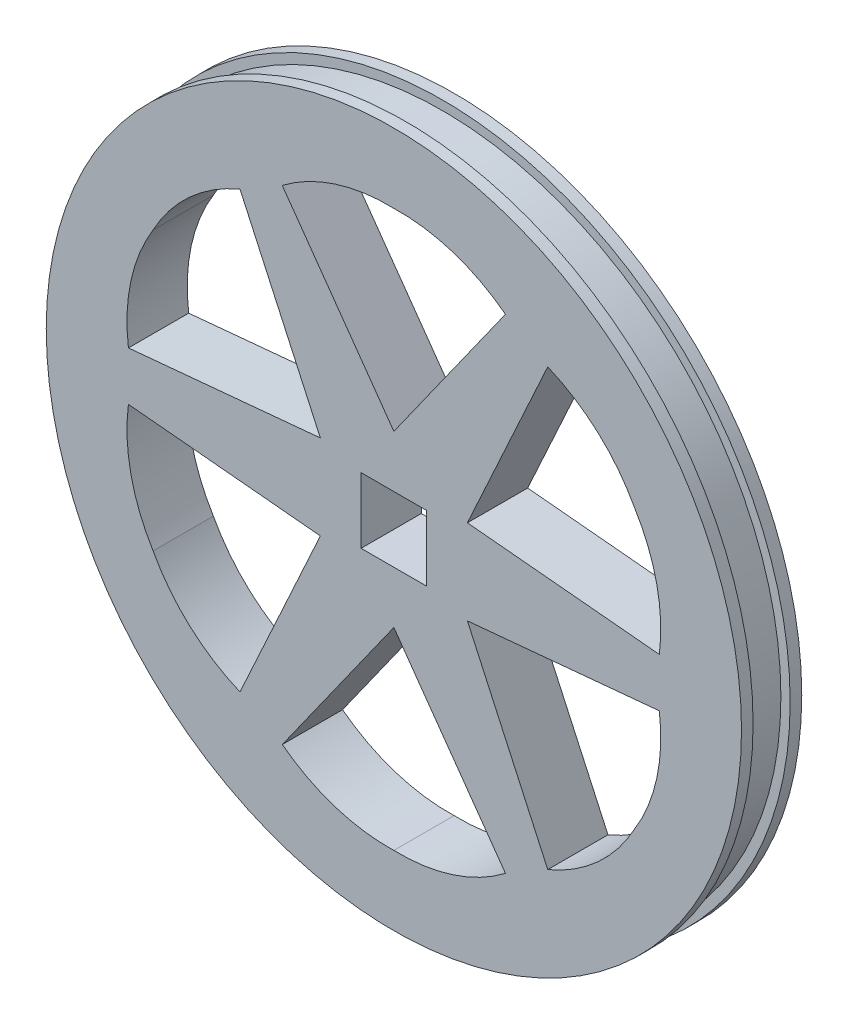
SolidWorks part; units mm, degrees
ref_plane "Front Plane" through (0, 0, 0) normal (0, 0, 1) x (1, 0, 0)
ref_plane "Top Plane" through (0, 0, 0) normal (0, 1, 0) x (1, 0, 0)
ref_plane "Right Plane" through (0, 0, 0) normal (1, 0, 0) x (0, 0, -1)
sketch "Sketch1" plane through (0, 0, 0) normal (0, 0, 1) x (1, 0, 0)
  line L1 (3.5355, -3.5355) -> (-3.5355, -3.5355)
  line L2 (3.5355, -3.5355) -> (3.5355, 3.5355)
  line L3 (3.5355, 3.5355) -> (-3.5355, 3.5355)
  line L4 (-3.5355, -3.5355) -> (-3.5355, 3.5355)
  line L5 (3.5355, -3.5355) -> (-3.5355, 3.5355) construction
  line L6 (3.5355, 3.5355) -> (-3.5355, -3.5355) construction
  circle A0 centre (0, 0) radius 37.5
  circle A1 centre (0, 0) radius 5 construction
  dimension "D1" = 75
  dimension "D2" = 10
extrude "Boss-Extrude1" add sketch "Sketch1" along normal mid plane 6.5
sketch "Sketch2" plane through (0, 0, 0) normal (0, 0, 1) x (1, 0, 0)
  line L0 (0, 0) -> (0, 32.5712) construction
  line L1 (0, 9.1586) -> (-12.0371, 26.1152)
  line L2 (0, 9.1586) -> (12.0371, 26.1152)
  arc A0 (-12.0371, 26.1152) -> (0, 29.9881) centre (-0.5568, 11.0765) cw
  arc A1 (12.0371, 26.1152) -> (0, 29.9881) centre (0.5568, 11.0765) ccw
extrude "Cut-Extrude1" cut sketch "Sketch2" along normal mid plane 8
pattern_circular "CirPattern1" count 6 over 360 about axis through (0, 0, 3.25) along (0, 0, -1) of "Cut-Extrude1" reverse direction yes
sketch "Sketch3" plane through (0, 0, 0) normal (0, 0, 1) x (1, 0, 0)
  circle A0 centre (0, 0) radius 37.5
  circle A1 centre (0, 0) radius 36.5
  circle A2 centre (0, 0) radius 37.5 construction
  dimension "D1" = 1
extrude "Cut-Extrude2" cut sketch "Sketch3" against normal mid plane 4
